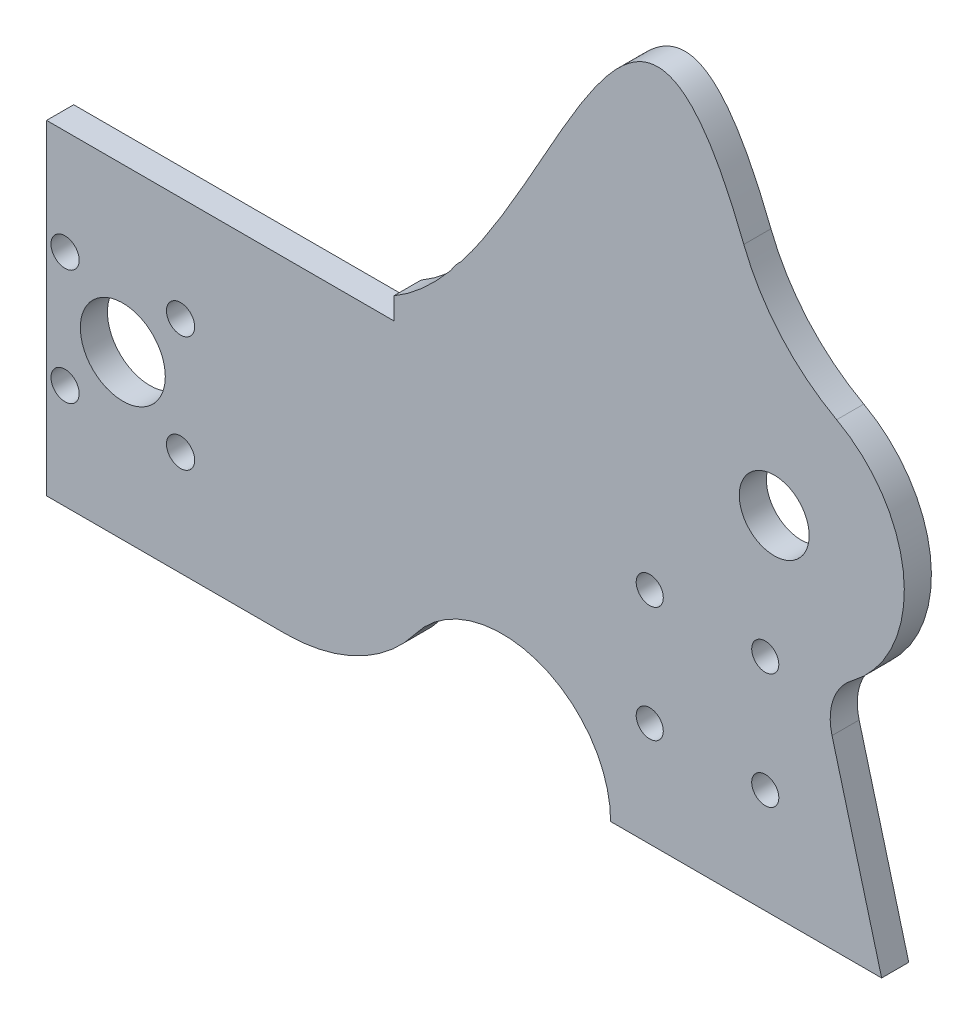
SolidWorks part; units mm, degrees
ref_plane "Front Plane" through (0, 0, 0) normal (0, 0, 1) x (1, 0, 0)
ref_plane "Top Plane" through (0, 0, 0) normal (0, 1, 0) x (1, 0, 0)
ref_plane "Right Plane" through (0, 0, 0) normal (1, 0, 0) x (0, 0, -1)
sketch "Sketch1" plane through (0, 0, 0) normal (0, 0, 1) x (1, 0, 0)
  line L0 (0, 0) -> (107.95, 0)
  line L3 (0, 38.1) -> (0, 25.4)
  line L4 (95.3675, 55.88) -> (0, 38.1)
  line L5 (0, 19.05) -> (100.2273, 19.05) construction
  line L6 (19.05, 19.05) -> (19.05, 28.62) construction
  line L7 (19.05, 19.05) -> (25.817, 25.817) construction
  line L8 (107.95, 0) -> (100.9363, 26.1756)
  line L10 (0, 12.7) -> (0, 0)
  line L11 (0, 25.4) -> (-7.62, 25.4)
  line L13 (0, 12.7) -> (-7.62, 12.7)
  line L14 (-7.62, 25.4) -> (-7.62, 12.7)
  line L15 (100.9363, 26.1756) -> (100.8688, 26.4276)
  arc A0 (100.8688, 26.4276) -> (95.3675, 55.88) centre (95.3675, 40.64) ccw
  circle A1 centre (95.3675, 40.64) radius 4.0957
  circle A2 centre (19.05, 19.05) radius 9.57 construction
  circle A3 centre (25.817, 25.817) radius 1.651
  circle A4 centre (25.817, 12.283) radius 1.651
  circle A5 centre (12.283, 12.283) radius 1.651
  circle A6 centre (12.283, 25.817) radius 1.651
  point P26 (19.05, 19.05)
  dimension "D1" = 8.1915
  dimension "D5" = 15.24
  dimension "D4" = 19.14
  dimension "D7" = 3.302
  dimension "D11" = 97.0107
  dimension "D2" = 38.1
  dimension "D3" = 40.64
  dimension "D6" = 107.95
  dimension "D8" = 45
  dimension "D9" = 4
  dimension "D10" = 19.05
  dimension "D12" = 75
  dimension "D14" = 12.7
  dimension "D15" = 12.7
  dimension "D16" = 7.62
extrude "Boss-Extrude1" add sketch "Sketch1" along normal blind 3.175
sketch "Sketch2" plane through (0, 0, 3.175) normal (0, 0, 1) x (1, 0, 0)
  circle A0 centre (95.3675, 40.64) radius 38.1 construction
sketch "Sketch6" plane through (0, 0, 3.175) normal (0, 0, 1) x (1, 0, 0)
  line L0 (0, 0) -> (107.95, 0) construction
  line L1 (50.8, 0) -> (76.2, 0)
  arc A0 (76.2, 0) -> (50.8, 0) centre (63.5, 0) ccw
  dimension "D1" = 25.4
  dimension "D2" = 31.75
extrude "Cut-Extrude2" cut sketch "Sketch6" against normal blind 6.35
sketch "Sketch7" plane through (0, 0, 3.175) normal (0, 0, 1) x (1, 0, 0)
  line L0 (12.283, 25.817) -> (25.817, 12.283) construction
  line L1 (12.283, 12.283) -> (25.817, 25.817) construction
  circle A0 centre (19.05, 19.05) radius 4.9784
  circle A2 centre (80.7829, 12.2536) radius 1.5875
  circle A3 centre (94.316, 12.2536) radius 1.5875
  circle A4 centre (80.7829, 25.7876) radius 1.5875
  circle A5 centre (94.316, 25.7876) radius 1.5875
  dimension "D1" = 9.9568
extrude "Cut-Extrude3" cut sketch "Sketch7" against normal through all
fillet "Fillet1" radius 6.35 1 edges at (100.8688, 26.4276, 1.5875)
sketch "Sketch8" plane through (0, 0, 3.175) normal (0, 0, 1) x (1, 0, 0)
  line L1 (0, 38.1) -> (50.8, 38.1)
  line L2 (0, 38.1) -> (0, 50.8)
  line L3 (0, 50.8) -> (50.8, 50.8)
  line L4 (50.8, 38.1) -> (50.8, 50.8)
  dimension "D1" = 50.8
  dimension "D2" = 12.7
extrude "Cut-Extrude4" cut sketch "Sketch8" against normal blind 50.8
sketch "Sketch9" plane through (0, 0, 3.175) normal (0, 0, 1) x (1, 0, 0)
  line L3 (50.8, 40.64) -> (57.15, 40.64)
  line L5 (57.15, 40.64) -> (50.8, 40.64)
  line L6 (57.15, 40.64) -> (57.15, 50.8)
  line L7 (57.15, 50.8) -> (50.8, 50.8)
  line L8 (50.8, 40.64) -> (50.8, 50.8)
  line L9 (0, 38.1) -> (50.8, 38.1) construction
  line M8 (50.8, 47.571) -> (50.8, 38.1)
  line M21 (95.3675, 55.88) -> (50.8, 47.571)
  dimension "D1" = 10.16
  dimension "D2" = 2.54
  dimension "D3" = 6.35
extrude "Cut-Extrude5" cut sketch "Sketch9" against normal blind 19.304 contours L3 L6 M21 M8 region at (54.0583, 44.4092, 3.175)
fillet "Fillet6" radius 6.35 1 edges at (57.15, 40.64, 1.5875)
fillet "Fillet7" radius 6.35 1 edges at (57.15, 48.7549, 1.5875)
fillet "Fillet8" radius 19.05 1 edges at (50.8, 0, 1.5875)
sketch "Sketch12" plane through (0, 0, 3.175) normal (0, 0, 1) x (1, 0, 0)
  line L0 (107.95, 0) -> (146.812, 0) construction
  line L1 (8.0257, 45.4128) -> (80.6683, 75.7903) construction
  line L2 (95.3675, 40.64) -> (80.6683, 75.7903) construction
  line L3 (80.6683, 75.7903) -> (79.4434, 78.7195) construction
  line L4 (50.8, 40.64) -> (85.0271, 40.64)
  line L5 (85.0271, 40.64) -> (95.3675, 55.88)
  arc A0 (61.8128, 49.6242) -> (56.8883, 45.1859) centre (62.9766, 43.3817) ccw construction
  circle A1 centre (19.05, 19.05) radius 28.575 construction
  circle A2 centre (95.3675, 40.64) radius 38.1 construction
  circle A3 centre (80.6683, 75.7903) radius 3.175 construction
  spline S0 degree 3 poles (50.8, 40.64) (70.7778, 52.1788) (78.5943, 111.5434) (95.3675, 55.88) knots 0 0 0 0 1 1 1 1
  dimension "D2" = 6.35
  dimension "D1" = 38.862
extrude "Boss-Extrude2" add sketch "Sketch12" against normal blind 3.175
fillet "Fillet9" radius 24.13 1 edges at (95.3675, 55.88, 1.5875)
sketch "Sketch13" plane through (0, 38.1, 0) normal (0, 1, 0) x (1, 0, 0)
  line L0 (10.12, -3.175) -> (10.12, 0)
  line L1 (0, -3.175) -> (50.8, -3.175) construction
  line L2 (0, 0) -> (50.8, 0) construction
  line L3 (10.12, 0) -> (-7.62, 0)
  line L4 (-7.62, 0) -> (-7.62, -3.175)
  line L5 (-7.62, -3.175) -> (10.12, -3.175)
extrude "Cut-Extrude6" cut sketch "Sketch13" against normal through all
